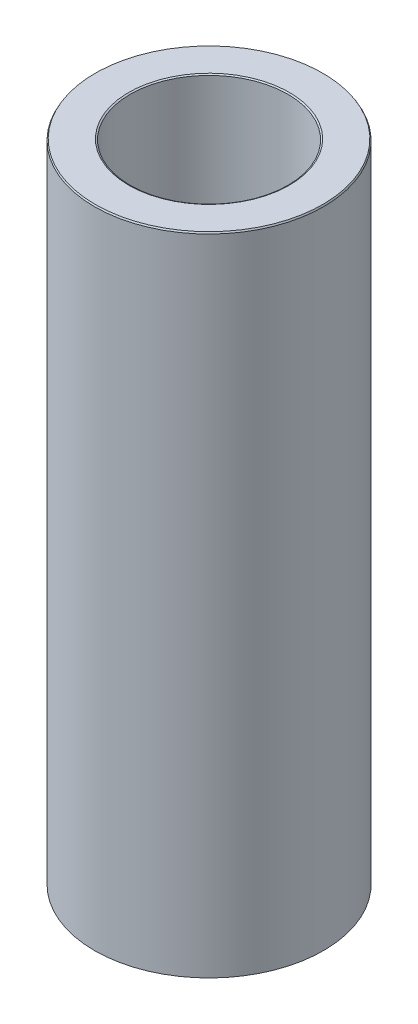
SolidWorks part; units mm, degrees
ref_plane "Front Plane" through (0, 0, 0) normal (0, 0, 1) x (1, 0, 0)
ref_plane "Top Plane" through (0, 0, 0) normal (0, 1, 0) x (1, 0, 0)
ref_plane "Right Plane" through (0, 0, 0) normal (1, 0, 0) x (0, 0, -1)
sketch "Sketch1" plane through (0, 0, 0) normal (0, 1, 0) x (1, 0, 0)
  circle A0 centre (0, 0) radius 45
  dimension "SLEEVE_OD" = 90
extrude "Boss-Extrude1" add sketch "Sketch1" along normal blind 253.9031
sketch "Sketch2" plane through (0, 0, 0) normal (0, 1, 0) x (1, 0, 0)
  circle A0 centre (0, 0) radius 30.9794
  dimension "BORE_D" = 61.9587
extrude "Cut-Extrude1" cut sketch "Sketch2" along normal through all
chamfer "Chamfer1" distance 0.5791 angle 30 4 edges at (0, 253.9031, 30.9794) (0, 0, 30.9794) (0, 0, 45) (0, 253.9031, 45) first distance on face at (0, 253.9031, 30.9794) first distance on face at (0, 0, 30.9794) first distance on face at (0, 253.9031, 45)
